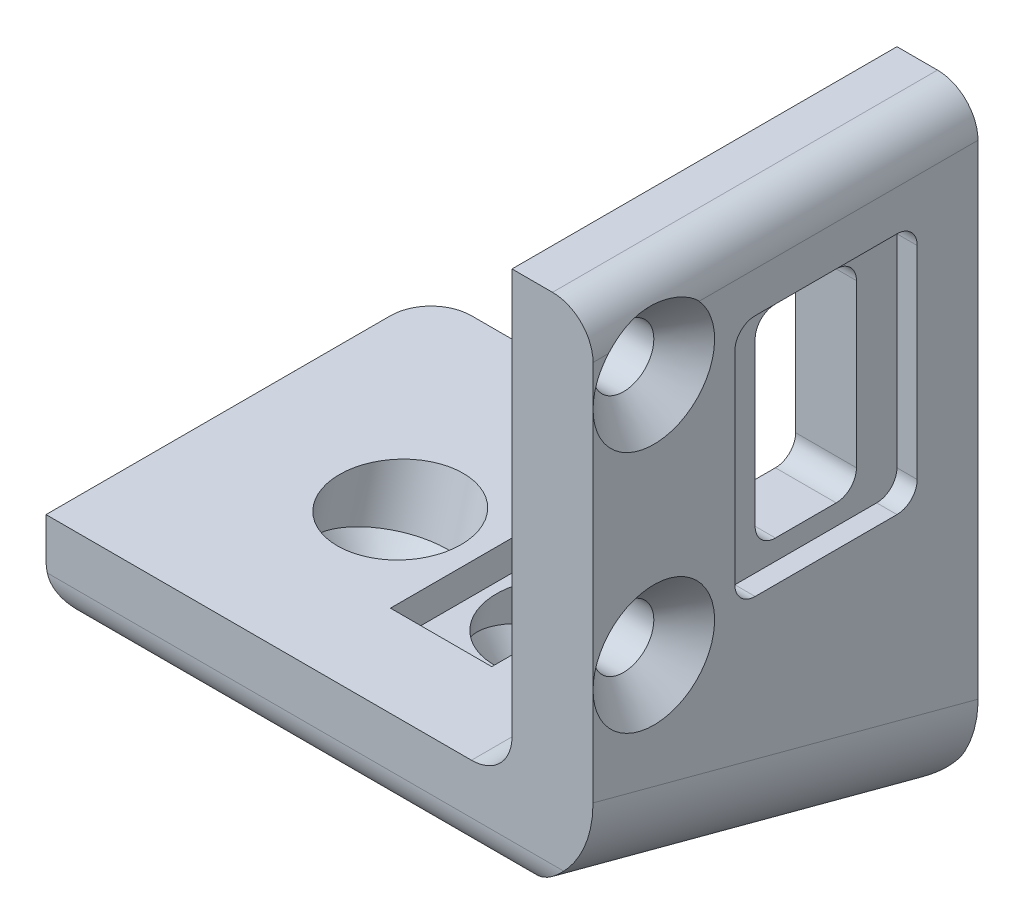
SolidWorks part; units mm, degrees
ref_plane "前视基准面" through (0, 0, 0) normal (0, 0, 1) x (1, 0, 0)
ref_plane "上视基准面" through (0, 0, 0) normal (0, 1, 0) x (1, 0, 0)
ref_plane "右视基准面" through (0, 0, 0) normal (1, 0, 0) x (0, 0, -1)
sketch "草图1" plane through (0, 0, 0) normal (0, 1, 0) x (1, 0, 0)
  line L1 (-13.5, 7.5) -> (13.5, 7.5)
  line L2 (-13.5, 7.5) -> (-13.5, -7.5)
  line L3 (-13.5, -7.5) -> (13.5, -7.5)
  line L4 (13.5, 7.5) -> (13.5, -7.5)
  line L5 (-13.5, 7.5) -> (13.5, -7.5) construction
  line L6 (-13.5, -7.5) -> (13.5, 7.5) construction
  point P0 (0, 0)
  dimension "D1" = 27
  dimension "D2" = 15
extrude "凸台-拉伸1" add sketch "草图1" along normal blind 8
sketch "草图13" plane through (13.5, 0, 0) normal (1, 0, 0) x (0, 0, -1)
  line L0 (-7.5, 4) -> (7.5, 0)
  line L1 (-7.5, 8) -> (-7.5, 0) construction
  line L2 (7.5, 0) -> (-7.5, 0)
  line L3 (-7.5, 0) -> (-7.5, 4)
extrude "切除-拉伸8" cut sketch "草图13" against normal blind 41.5
sketch "草图5" plane through (0, 8, 0) normal (0, 1, 0) x (1, 0, 0)
  line L0 (-13.5, -7.5) -> (13.5, -7.5) construction
  line L4 (9.5, -7.5) -> (9.5, 7.5) construction
  line L12 (13.5, 7.5) -> (9.5, 7.5)
  line L13 (13.5, 7.5) -> (13.5, -7.5)
  line L14 (13.5, -7.5) -> (9.5, -7.5)
  line L15 (9.5, 7.5) -> (9.5, -7.5)
  point P0 (0, 0)
  dimension "D1" = 4
extrude "凸台-拉伸3" add sketch "草图5" along normal blind 24
sketch "草图7" plane through (0, 8, 0) normal (0, 1, 0) x (1, 0, 0)
  line L1 (4, 3.5) -> (-1, 3.5)
  line L2 (4, 3.5) -> (4, -3)
  line L3 (4, -3) -> (-1, -3)
  line L4 (-1, 3.5) -> (-1, -3)
  line L6 (9.5, 7.5) -> (9.5, -7.5) construction
  line L7 (9.5, 7.5) -> (-13.5, 7.5) construction
  dimension "D1" = 10.5
  dimension "D2" = 5
  dimension "D3" = 10.5
  dimension "D4" = 4
extrude "切除-拉伸5" cut sketch "草图7" against normal blind 1.5
sketch "草图10" plane through (13.5, 0, 0) normal (-1, 0, 0) x (0, 0, 1)
  line L0 (4.5, 32) -> (4.5, 8) construction
  line L1 (-7.5, 32) -> (7.5, 32) construction
  line L4 (7.5, 20) -> (-7.5, 20) construction
  line L5 (7.5, 8) -> (-7.5, 8) construction
  line L6 (7.5, 8) -> (7.5, 4) construction
  line L7 (-7.5, 8) -> (-7.5, 0) construction
  line L8 (7.5, 8) -> (-7.5, 8) construction
  line L9 (7.5, 32) -> (7.5, 4) construction
  line L11 (7.5, 32) -> (7.5, 8) construction
  circle A0 centre (4.5, 20) radius 1.5
  circle A1 centre (4.5, 26) radius 1.5
  circle A2 centre (4.5, 14) radius 1.5
  dimension "D1" = 6
  dimension "D3" = 3
  dimension "D2" = 6
  dimension "D4" = 24
extrude "切除-拉伸6" cut sketch "草图10" along normal blind 21.5 contours A2 | A1
sketch "草图12" plane through (9.5, 0, 0) normal (-1, 0, 0) x (0, 0, 1)
  line L0 (-6.6954, 20) -> (-1.3046, 20) construction
  line L1 (4.5, 26) -> (4.5, 14) construction
  line L2 (-1.3046, 20) -> (-4, 32) construction
  line L3 (-7.5, 32) -> (7.5, 32) construction
  line L4 (-4, 32) -> (-4, 8) construction
  line L5 (-7.5, 8) -> (7.5, 8) construction
  line L6 (7.5, 32) -> (7.5, 8) construction
  line L7 (4.5, 20) -> (-4, 20) construction
  line L8 (-6.5, 15) -> (-1.5, 15)
  line L9 (-6.5, 15) -> (-6.5, 25)
  line L10 (-6.5, 25) -> (-1.5, 25)
  line L11 (-1.5, 15) -> (-1.5, 25)
  line L12 (-6.5, 15) -> (-1.5, 25) construction
  line L13 (-6.5, 25) -> (-1.5, 15) construction
  point P12 (-4, 20)
  point P22 (0, 0)
  dimension "D1" = 11.5
  dimension "D2" = 10
  dimension "D3" = 5
extrude "切除-拉伸7" cut sketch "草图12" against normal blind 21.5
sketch "草图14" plane through (0, 0, 7.5) normal (0, 0, 1) x (1, 0, 0)
  line L0 (13.5, 32) -> (13.5, 4) construction
  line L1 (9.5, 32) -> (13.5, 32)
  line L2 (9.5, 32) -> (9.5, 30)
  line L3 (9.5, 30) -> (13.5, 30)
  line L4 (13.5, 32) -> (13.5, 30)
  dimension "D1" = 2
extrude "切除-拉伸9" cut sketch "草图14" against normal blind 21.5
sketch "草图15" plane through (0, 1.8672, -0.4979) normal (0, -0.9662, 0.2577) x (1, 0, 0)
  line L0 (2.5, 0) -> (-20.9033, 0) construction
  line L2 (-4.9715, 0.6537) -> (-4.9715, 0) construction
  line L3 (2.5, 0) -> (-4.9715, 0.6537) construction
  circle A0 centre (-4.9715, 0.6537) radius 1.5
  circle A1 centre (2.5, 0) radius 1.5
  dimension "D3" = 5
  dimension "D1" = 2.5
  dimension "D2" = 7.5
extrude "切除-拉伸10" cut sketch "草图15" against normal blind 21.5
ref_plane "基准面4" through (0, 6.6984, -1.7862) normal (0, -0.9662, 0.2577) x (-1, 0, 0)
sketch "草图21" plane through (0, 0, -7.5) normal (0, 0, -1) x (-1, 0, 0)
  line L0 (-9.5, 8) -> (13.5, 8) construction
  line L5 (-13.5, -1.9871) -> (11.8284, -1.9871)
  line L6 (-13.5, -1.9871) -> (-13.5, 8)
  line L7 (-9.5, 8) -> (13.5, 8)
  line L10 (13.5, 8) -> (13.5, -1.9871)
  line L11 (13.5, -1.9871) -> (11.8284, -1.9871)
  line L17 (-13.5, 30) -> (-13.5, 0) construction
  line L20 (-13.5, 8) -> (-13.5, 30)
  line L21 (-13.5, 30) -> (-9.5, 30)
  line L22 (-9.5, 8) -> (-9.5, 30)
extrude "凸台-拉伸6" add sketch "草图21" along normal blind 4
sketch "草图17" plane through (0, 6.6984, -1.7862) normal (0, -0.9662, 0.2577) x (-1, 0, 0)
  circle A0 centre (-2.5, 0) radius 3
extrude "切除-拉伸13" cut sketch "草图17" against normal blind 12 and the other way blind 1.5
sketch "草图19" plane through (0, 6.6984, -1.7862) normal (0, -0.9662, 0.2577) x (-1, 0, 0)
  circle A0 centre (4.9715, -0.6537) radius 3
extrude "切除-拉伸15" cut sketch "草图19" against normal blind 2.5 and the other way blind 1
sketch "草图22" plane through (13.5, 0, 0) normal (1, 0, 0) x (0, 0, -1)
  line L0 (-7.5, 4) -> (7.5, 0)
  line L1 (7.5, 0) -> (11.5, -1.0667)
  line L3 (11.5, -1.0667) -> (11.5, -3.2675)
  line L4 (11.5, -3.2675) -> (3.7364, -2.5789)
  line L5 (3.7364, -2.5789) -> (-7.5, 4)
  line L6 (11.5, 30) -> (11.5, -1.9871) construction
extrude "切除-拉伸16" cut sketch "草图22" against normal blind 54
sketch "草图23" plane through (13.5, 0, 0) normal (-1, 0, 0) x (0, 0, 1)
  line L0 (-1.5, 15) -> (-1.5, 25) construction
  line L1 (0.5, 26) -> (-8.5, 26)
  line L2 (0.5, 26) -> (0.5, 14)
  line L3 (0.5, 14) -> (-8.5, 14)
  line L4 (-8.5, 26) -> (-8.5, 14)
  line L6 (-6.5, 25) -> (-6.5, 15) construction
  line L7 (-1.5, 25) -> (-6.5, 25) construction
  line L8 (-6.5, 15) -> (-1.5, 15) construction
  dimension "D1" = 2
  dimension "D2" = 2
  dimension "D3" = 1
  dimension "D4" = 1
extrude "切除-拉伸17" cut sketch "草图23" along normal blind 1
fillet "圆角2" radius 2 1 edges at (9.5, 8, -2)
fillet "圆角3" radius 2 1 edges at (13.5, 30, -2)
fillet "圆角4" radius 5 1 edges at (13.5, 1.4667, -2)
chamfer "倒角1" distance 1.5 angle 45 4 edges at (2.5, 4.8625, -2.8491) (13.5, 14, 3) (13.5, 26, 3) (-4.9715, 5.5141, -2.3463)
fillet "圆角5" radius 2 4 edges at (-13.5, 1.4667, -2) (-2.5, 4, 7.5) (-2.5, -1.0667, -11.5) (-13.5, 3.4667, -11.5)
fillet "圆角8" radius 1 8 edges at (13, 26, -8.5) (13, 14, -8.5) (13, 14, 0.5) (13, 26, 0.5) (11, 15, -6.5) (11, 25, -6.5) (11, 25, -1.5) (11, 15, -1.5)
